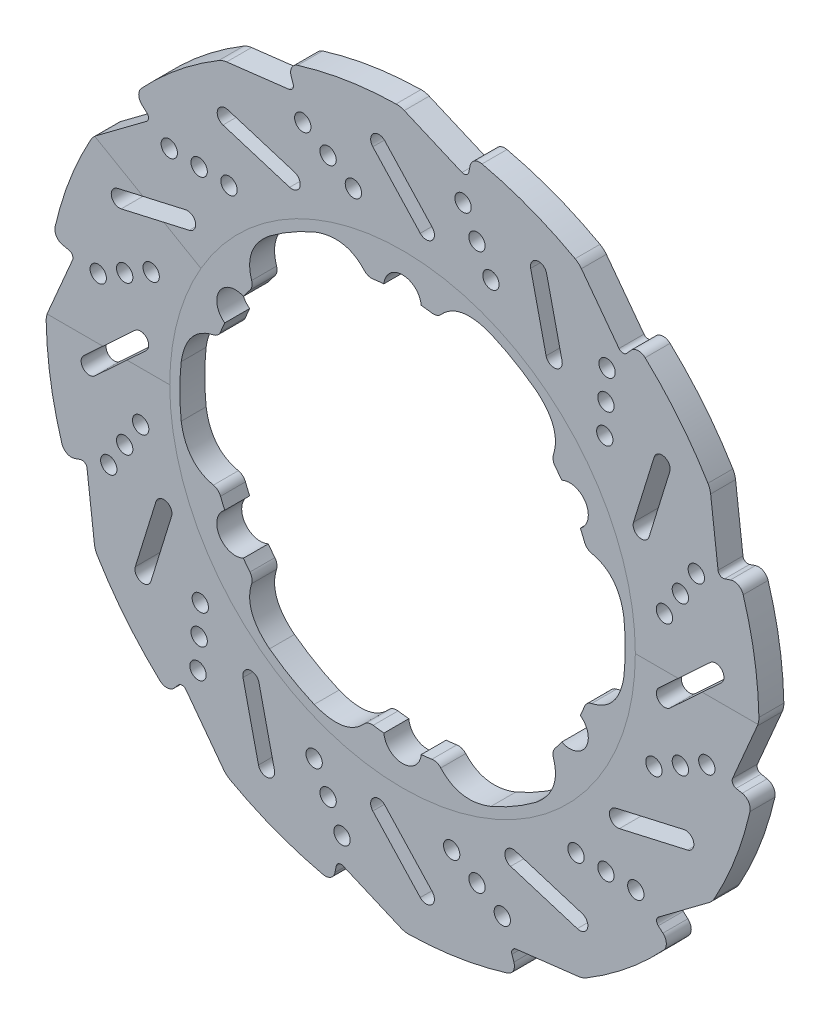
SolidWorks part; units mm, degrees
ref_plane "Front Plane" through (0, 0, 0) normal (0, 0, 1) x (1, 0, 0)
ref_plane "Top Plane" through (0, 0, 0) normal (0, 1, 0) x (1, 0, 0)
ref_plane "Right Plane" through (0, 0, 0) normal (1, 0, 0) x (0, 0, -1)
sketch "Sketch1" plane through (0, 0, 0) normal (0, 0, 1) x (1, 0, 0)
  circle A0 centre (0, 0) radius 90.805
  circle A1 centre (0, 0) radius 56.769
  dimension "D1" = 181.61
  dimension "D2" = 34.036
extrude "RotorBody" add sketch "Sketch1" along normal blind 6.35
sketch "Sketch2" plane through (0, 0, 6.35) normal (0, 0, 1) x (1, 0, 0)
  line L0 (0, 49.149) -> (0, 56.6) construction
  circle A0 centre (0, 0) radius 49.149 construction
  circle A1 centre (0, 49.149) radius 4.7625
  circle A2 centre (0, 0) radius 49.784
  circle A4 centre (0, 0) radius 56.769 construction
  spline S0 degree 2 poles (-8.89, 48.9838) (-14.5829, 56.567) (-25.4, 50.7697) knots 0 0 0 1 1 1
  spline S1 degree 2 poles (8.89, 48.9838) (14.5829, 56.567) (25.4, 50.7697) knots 0 0 0 1 1 1
  point P13 (-25.4, 49.947)
  point P14 (0, 0)
  point P15 (-25.4, 50.7697)
  point P16 (-25.4, 50.7697)
  point P17 (0, 0)
  point P20 (-25.4, 50.7697)
  point P21 (-25.4, 50.7697)
  point P22 (0, 0)
  point P23 (0, 0)
  circle M2 centre (0, 0) radius 56.769
  dimension "D1" = 98.298
  dimension "D2" = 9.525
  dimension "D4" = 8.89
  dimension "D5" = 11.43
  dimension "D6" = 25.4
  dimension "D7" = 2.54
  dimension "D3" = 0.635
extrude "FloatPinIF" add sketch "Sketch2" against normal through all contours A2 S1 S0 A1 M2 region at (0, 54.3683, 6.35)
pattern_circular "FloatPinPattern" count 6 over 360 about axis through (0, 0, 6.35) along (0, 0, -1) of "FloatPinIF" reverse direction yes
sketch "Sketch3" plane through (0, 0, 6.35) normal (0, 0, 1) x (1, 0, 0)
  line L0 (-6.0411, 79.801) -> (6.0411, 66.757) construction
  line L1 (-6.0411, 79.801) -> (0, 0) construction
  line L2 (0, 0) -> (6.0411, 66.757) construction
  line L3 (-7.5691, 78.3857) -> (4.5131, 65.3416)
  line L4 (-4.5131, 81.2164) -> (7.5691, 68.1723)
  line L5 (15.4112, 77.5221) -> (22.5208, 64.042) construction
  line L6 (34.6688, 72.1303) -> (38.6102, 54.7927) construction
  line L7 (52.1562, 60.6996) -> (51.476, 42.9326) construction
  line L8 (66.0892, 45.1323) -> (60.8338, 28.1467) construction
  line L9 (75.5183, 26.4893) -> (66.0458, 11.4427) construction
  line L10 (79.801, 6.0411) -> (66.757, -6.0411) construction
  line L11 (78.6454, -14.8188) -> (62.9187, -23.1132) construction
  line L12 (72.1303, -34.6688) -> (54.7927, -38.6102) construction
  line L13 (60.6996, -52.1562) -> (42.9326, -51.476) construction
  line L14 (45.1323, -66.0892) -> (28.1467, -60.8338) construction
  line L15 (26.4893, -75.5183) -> (11.4427, -66.0458) construction
  line L16 (6.0411, -79.801) -> (-6.0411, -66.757) construction
  line L17 (-14.8188, -78.6454) -> (-23.1132, -62.9187) construction
  line L18 (-34.6688, -72.1303) -> (-38.6102, -54.7927) construction
  line L19 (-52.1562, -60.6996) -> (-51.476, -42.9326) construction
  line L20 (-66.0892, -45.1323) -> (-60.8338, -28.1467) construction
  line L21 (-75.5183, -26.4893) -> (-66.0458, -11.4427) construction
  line L22 (-79.801, -6.0411) -> (-66.757, 6.0411) construction
  line L23 (-78.6454, 14.8188) -> (-62.9187, 23.1132) construction
  line L24 (-72.1303, 34.6688) -> (-54.7927, 38.6102) construction
  line L25 (-60.6996, 52.1562) -> (-42.9326, 51.476) construction
  line L26 (-45.1323, 66.0892) -> (-28.1467, 60.8338) construction
  line L27 (-26.4893, 75.5183) -> (-11.4427, 66.0458) construction
  line L28 (18.966, 70.7821) -> (0, 0) construction
  line L29 (0, 0) -> (0, 73.279) construction
  circle A0 centre (0, 0) radius 59.309
  circle A1 centre (0, 0) radius 90.805 construction
  circle A2 centre (0, 0) radius 73.279 construction
  arc A3 (-7.5691, 78.3857) -> (-4.5131, 81.2164) centre (-6.0411, 79.801) cw
  arc A4 (4.5131, 65.3416) -> (7.5691, 68.1723) centre (6.0411, 66.757) ccw
  circle A5 centre (15.4112, 77.5221) radius 2.0828
  circle A6 centre (22.5208, 64.042) radius 2.0828
  circle A7 centre (18.966, 70.7821) radius 2.0828
  point P8 (0, 73.279)
  point P64 (0, 0)
  dimension "D1" = 31.496
  dimension "D2" = 13.97
  dimension "D8" = 4.1656
  dimension "D9" = 4.1656
  dimension "D10" = 4.1656
  dimension "D3" = 17.78
  dimension "D4" = 9.5
  dimension "D11" = 15
  dimension "D7" = 15.24
  dimension "D5" = 2.0828
  dimension "D6" = 2.0828
extrude "Slot+Holes" cut sketch "Sketch3" against normal through all contours A5 | A7 | A6 | L3 A4 L4 A3 region at (15.4112, 77.5221, 6.35) region at (22.5208, 64.042, 6.35) region at (18.966, 70.7821, 6.35)
pattern_circular "Slot+HolesPattern" count 12 over 360 about axis through (0, 0, 6.35) along (0, 0, -1) of "Slot+Holes" reverse direction yes
sketch "Sketch5" plane through (0, 0, 6.35) normal (0, 0, 1) x (1, 0, 0)
  line L0 (-25.4145, 74.8417) -> (-12.5175, 66.7224) construction
  line L3 (4.5589, 60.4742) -> (-38.4313, 87.5385)
  line L4 (4.5589, 60.4742) -> (0.4993, 54.0256)
  line L5 (-38.4313, 87.5385) -> (-42.491, 81.09)
  line L6 (0.4993, 54.0256) -> (-42.491, 81.09)
  line L7 (4.5589, 60.4742) -> (-42.491, 81.09) construction
  line L8 (-38.4313, 87.5385) -> (0.4993, 54.0256) construction
  line L19 (17.7025, 89.0627) -> (0, 0)
  line L20 (15.4112, 77.5221) -> (22.5208, 64.042) construction
  line L29 (44.9285, 78.9112) -> (56.0946, 63.9821)
  line L30 (0, 0) -> (16.5883, 83.4574) construction
  line L31 (10.4868, 95.0262) -> (34.1853, 50.0927) construction
  line L32 (10.4868, 95.0262) -> (3.7467, 91.4715)
  line L33 (34.1853, 50.0927) -> (27.4452, 46.5379)
  line L34 (3.7467, 91.4715) -> (27.4452, 46.5379) construction
  line L35 (10.4868, 95.0262) -> (27.4452, 46.5379) construction
  line L36 (34.1853, 50.0927) -> (3.7467, 91.4715) construction
  line L37 (-29.2006, 85.9818) -> (0, 0)
  line L38 (-0.5464, 90.8034) -> (16.5883, 83.4574)
  line L39 (7.4565, 65.2289) -> (-15.0676, 89.5462) construction
  arc A1 (16.8939, 84.9946) -> (15.1478, 84.075) centre (15.6482, 85.2422) cw
  circle A2 centre (0, 0) radius 85.09
  circle A3 centre (0, 0) radius 90.805 construction
  circle A4 centre (0, 0) radius 90.805
  arc A5 (17.2002, 86.5356) -> (20.2581, 88.5164) centre (19.6914, 86.0404) cw
  arc A6 (-1.6526, 90.79) -> (0.4415, 90.3798) centre (-1.5602, 85.7108) cw
  arc A7 (4.5131, 65.3416) -> (7.5691, 68.1723) centre (6.0411, 66.757) ccw construction
  point P16 (18.966, 70.7821)
  point P17 (-18.966, 70.7821)
  point P24 (-18.966, 70.7821)
  point P29 (0, 0)
  point P38 (16.5883, 83.4574)
  point P43 (18.966, 70.7821)
  point P49 (-27.3628, 80.5704)
  dimension "D6" = 50.8
  dimension "D7" = 170.18
  dimension "D3" = 181.61
  dimension "D10" = 2.54
  dimension "D11" = 1.27
  dimension "D12" = 5.08
  dimension "D1" = 7.62
  dimension "D2" = 7.62
  dimension "D4" = 50.8
  dimension "D5" = 2
  dimension "D8" = 14.5755
  dimension "D9" = 85.09
  dimension "D13" = 14.5755
extrude "PerimeterCutOut" cut sketch "Sketch5" against normal through all contours L19 A4 L38 region at (10.936, 88.0437, 6.35)
pattern_circular "PerimeterPattern" count 12 over 360 about axis through (0, 0, 6.35) along (0, 0, -1) of "PerimeterCutOut"
extrude "PerimeterFillet" cut sketch "Sketch5<5>" against normal through all contours L19 A5 A4 | A4 A6 L38 region at (-0.5717, 90.7166, 6.35) region at (18.1631, 88.3812, 6.35)
sketch "Sketch5<5>" plane through (0, 0, 6.35) normal (0, 0, 1) x (1, 0, 0) same geometry as "Sketch5"
pattern_circular "PFilletPattern" count 12 over 360 about axis through (0, 0, 6.35) along (0, 0, -1) of "PerimeterFillet" reverse direction yes
fillet "FloatPinIFFillets" radius 2.54 12 edges at (37.9762, 32.1909, 3.175) (46.8662, 16.7929, 3.175) (46.8662, -16.7929, 3.175) (37.9762, -32.1909, 3.175) (8.89, -48.9838, 3.175) (-8.89, -48.9838, 3.175) (-37.9762, -32.1909, 3.175) (-46.8662, -16.7929, 3.175) (-46.8662, 16.7929, 3.175) (-37.9762, 32.1909, 3.175) (8.89, 48.9838, 3.175) (-8.89, 48.9838, 3.175)
sketch "Sketch6" plane through (0, 0, 6.35) normal (0, 0, 1) x (1, 0, 0)
  line L0 (-90.805, 0) -> (-59.309, 0)
  line L1 (0, 0) -> (-51.3631, 29.6545) construction
  line L2 (-59.309, 0) -> (59.309, 0) construction
  line L3 (59.309, 0) -> (90.805, 0)
  line L4 (-51.3631, 29.6545) -> (-78.6394, 45.4025)
  circle A0 centre (0, 0) radius 59.309
  circle A1 centre (0, 0) radius 90.805
  point P6 (0, 0)
  point P8 (59.309, 0)
  point P9 (-51.3631, 29.6545)
  point P10 (-59.309, 0)
  point P11 (46.8464, 12.6598)
  dimension "D1" = 181.61
  dimension "D2" = 31.496
  dimension "D3" = 150
split line "SplitLine"
